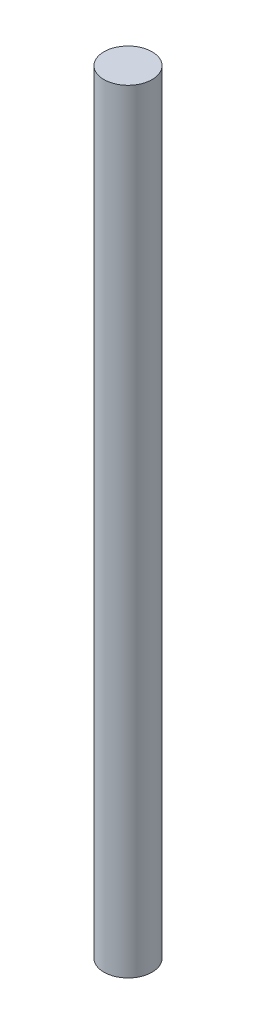
SolidWorks part; units mm, degrees
material "ALUMINUM 6061-T6"
ref_plane "Front Plane" through (0, 0, 0) normal (0, 0, 1) x (1, 0, 0)
ref_plane "Top Plane" through (0, 0, 0) normal (0, 1, 0) x (1, 0, 0)
ref_plane "Right Plane" through (0, 0, 0) normal (1, 0, 0) x (0, 0, -1)
sketch "Sketch1" plane through (0, 0, 0) normal (0, 1, 0) x (1, 0, 0)
  circle A0 centre (0, 0) radius 9.4996
extrude "Boss-Extrude1" add sketch "Sketch1" along normal mid plane 304.8
